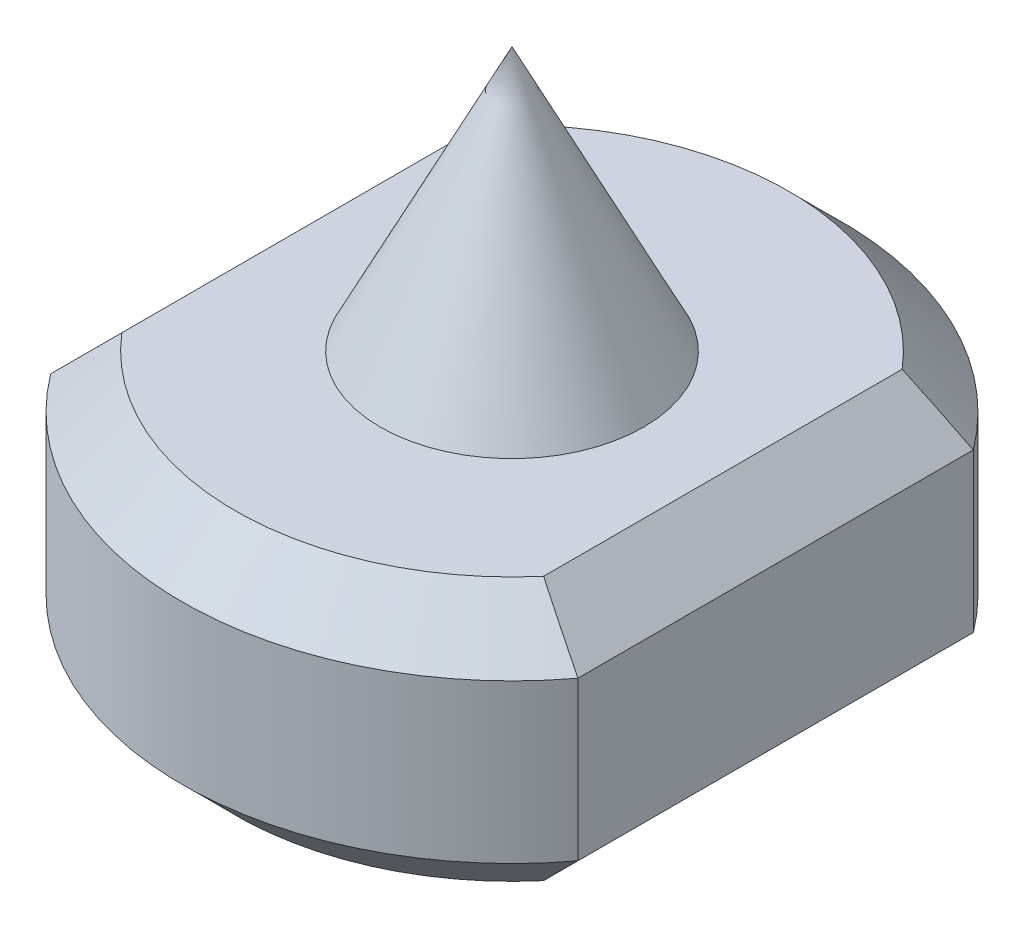
SolidWorks part; units mm, degrees
material "Custom Plastic"
ref_plane "Front Plane" through (0, 0, 0) normal (0, 0, 1) x (1, 0, 0)
ref_plane "Top Plane" through (0, 0, 0) normal (0, 1, 0) x (1, 0, 0)
ref_plane "Right Plane" through (0, 0, 0) normal (1, 0, 0) x (0, 0, -1)
sketch "Sketch1" plane through (0, 0, 0) normal (0, 1, 0) x (1, 0, 0)
  circle A0 centre (0, 0) radius 12.5
  dimension "D1" = 25
extrude "Boss-Extrude2" add sketch "Sketch1" along normal blind 10 contours A0
sketch "Sketch2" plane through (0, 0, 0) normal (0, 0, 1) x (1, 0, 0)
  line L0 (0, -1000) -> (0, 49000) construction
  line L1 (-12.5, 0) -> (12.5, 0) construction
  line L2 (5, 10) -> (0, 20)
  line L3 (0, 20) -> (0, 10)
  line L7 (12.5, 10) -> (-12.5, 10) construction
  line L8 (5, 10) -> (0, 10)
  point P5 (0, 0)
  dimension "D1" = 10
  dimension "D2" = 5
revolve "Revolve1" add sketch "Sketch2" angle 360 about L0
sketch "Sketch3" plane through (0, 0, 0) normal (0, 1, 0) x (1, 0, 0)
  line L0 (0, -1000) -> (0, 49000) construction
  line L1 (-10, 7.5) -> (-10, -7.5)
  line L2 (10, 7.5) -> (10, -7.5)
  circle A0 centre (0, 0) radius 12.5 construction
  arc A1 (-10, 7.5) -> (-10, -7.5) centre (0, 0) ccw
  arc A2 (10, -7.5) -> (10, 7.5) centre (0, 0) ccw
  dimension "D1" = 20
extrude "Cut-Extrude1" cut sketch "Sketch3" along normal up to next
chamfer "Chamfer1" distance 2 angle 45 8 edges at (0, 0, 12.5) (10, 0, 0) (0, 0, -12.5) (-10, 0, 0) (-10, 10, 0) (0, 10, -12.5) (10, 10, 0) (0, 10, 12.5)
